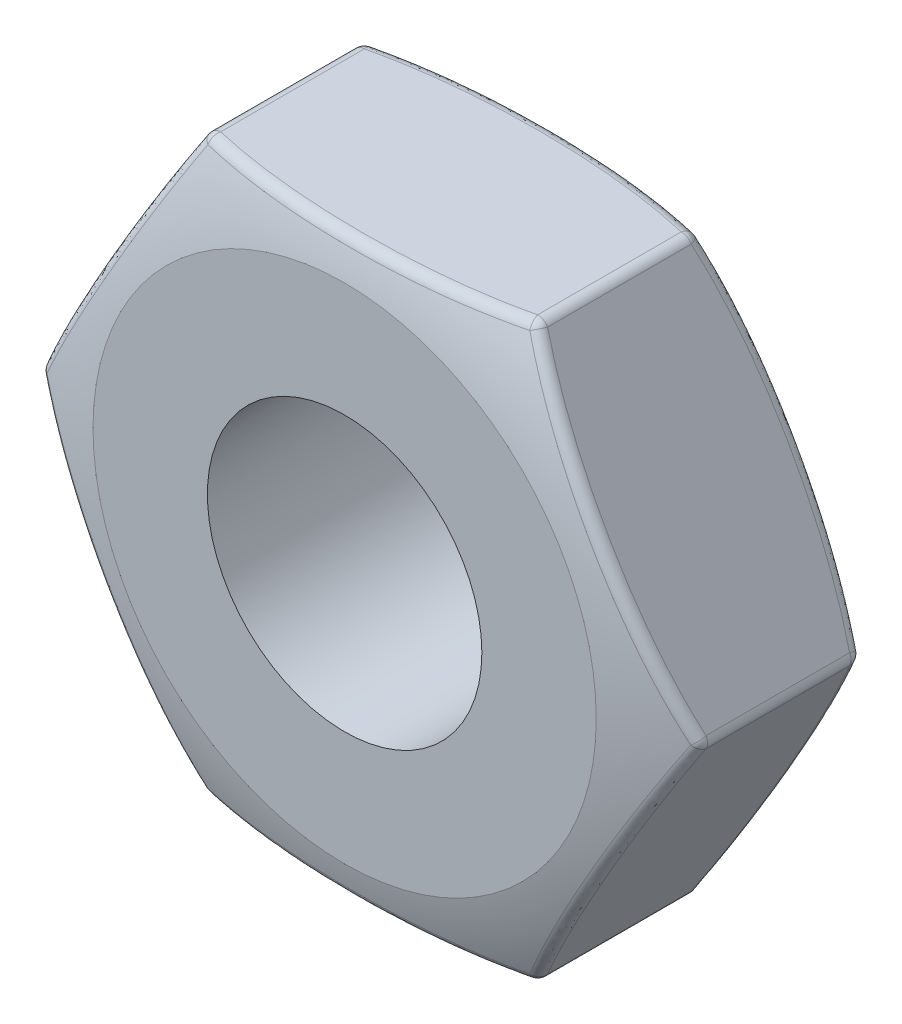
SolidWorks part; units mm, degrees
ref_plane "Front Plane" through (0, 0, 0) normal (0, 0, 1) x (1, 0, 0)
ref_plane "Top Plane" through (0, 0, 0) normal (0, 1, 0) x (1, 0, 0)
ref_plane "Right Plane" through (0, 0, 0) normal (1, 0, 0) x (0, 0, -1)
sketch "Sketch1" plane through (0, 0, 0) normal (0, 0, 1) x (1, 0, 0)
  line L1 (2.8868, 0) -> (1.4434, 2.5)
  line L2 (1.4434, 2.5) -> (-1.4434, 2.5)
  line L3 (-1.4434, 2.5) -> (-2.8868, 0)
  line L4 (-2.8868, 0) -> (-1.4434, -2.5)
  line L5 (-1.4434, -2.5) -> (1.4434, -2.5)
  line L6 (1.4434, -2.5) -> (2.8868, 0)
  circle A0 centre (0, 0) radius 2.5 construction
  dimension "D1" = 5
extrude "Extrude1" add sketch "Sketch1" along normal blind 1.86
sketch "Sketch2" plane through (0, 0, 0) normal (1, 0, 0) x (0, 0, -1)
  line L0 (1.0118, 0) -> (-3.858, 0) construction
  line L1 (0, 2.5) -> (0, 0) construction
  line L3 (-0.5, 3.3) -> (0.4733, 3.3)
  line L4 (0.4733, 3.3) -> (0.4733, 2.2)
  line L5 (0.4733, 2.2) -> (0, 2.2)
  line L6 (-1.86, 2.5) -> (-1.86, 0) construction
  line L7 (-1.36, 3.3) -> (-2.8363, 3.3)
  line L8 (-2.8363, 3.3) -> (-2.8363, 2.2)
  line L9 (-2.8363, 2.2) -> (-1.86, 2.2)
  arc A0 (0, 2.2) -> (-0.5, 3.3) centre (-2.9251, 1.534) ccw
  arc A1 (-1.36, 3.3) -> (-1.86, 2.2) centre (1.0651, 1.534) ccw
  dimension "D4" = 3
  dimension "D5" = 3.3
  dimension "D8" = 3
  dimension "D1" = 2.2
  dimension "D2" = 3.3
  dimension "D3" = 0.5
  dimension "D6" = 2.2
  dimension "D7" = 0.5
revolve "Cut-Revolve1" cut sketch "Sketch2" angle 360 about L0
sketch "Sketch3" plane through (0, 0, 1.86) normal (0, 0, 1) x (1, 0, 0)
  circle A0 centre (0, 0) radius 1.2
  dimension "D1" = 2.4
extrude "Cut-Extrude1" cut sketch "Sketch3" against normal blind 12.5
fillet "Fillet1" radius 0.1 6 edges at (-1.4434, 2.5, 0.93) (-2.8868, 0, 0.93) (-1.4434, -2.5, 0.93) (1.4434, -2.5, 0.93) (2.8868, 0, 0.93) (1.4434, 2.5, 0.93)
fillet "Fillet2" radius 0.1 24 edges at (-2.8708, 0.0099, 0.2394) (-1.4268, 2.4911, 0.2394) (1.444, 2.4812, 0.2394) (2.8708, -0.0099, 0.2394) (1.4268, -2.4911, 0.2394) (-1.444, -2.4812, 0.2394) (-1.4268, -2.4911, 1.6206) (1.444, -2.4812, 1.6206) (2.8708, 0.0099, 1.6206) (1.4268, 2.4911, 1.6206) (-1.444, 2.4812, 1.6206) (-2.8708, -0.0099, 1.6206) (2.4399, 0.7739, 1.7541) (1.8902, 1.7261, 0.1059) (2.4399, -0.7739, 0.1059) (0.9739, 2.5, -3.8364) (1.8902, -1.7261, 1.7541) (-0.9739, 2.5, 5.6964) (0.9739, -2.5, 5.6964) (-1.8902, 1.7261, 1.7541) (-0.9739, -2.5, -3.8364) (-2.4399, 0.7739, 0.1059) (-1.8902, -1.7261, 0.1059) (-2.4399, -0.7739, 1.7541)
